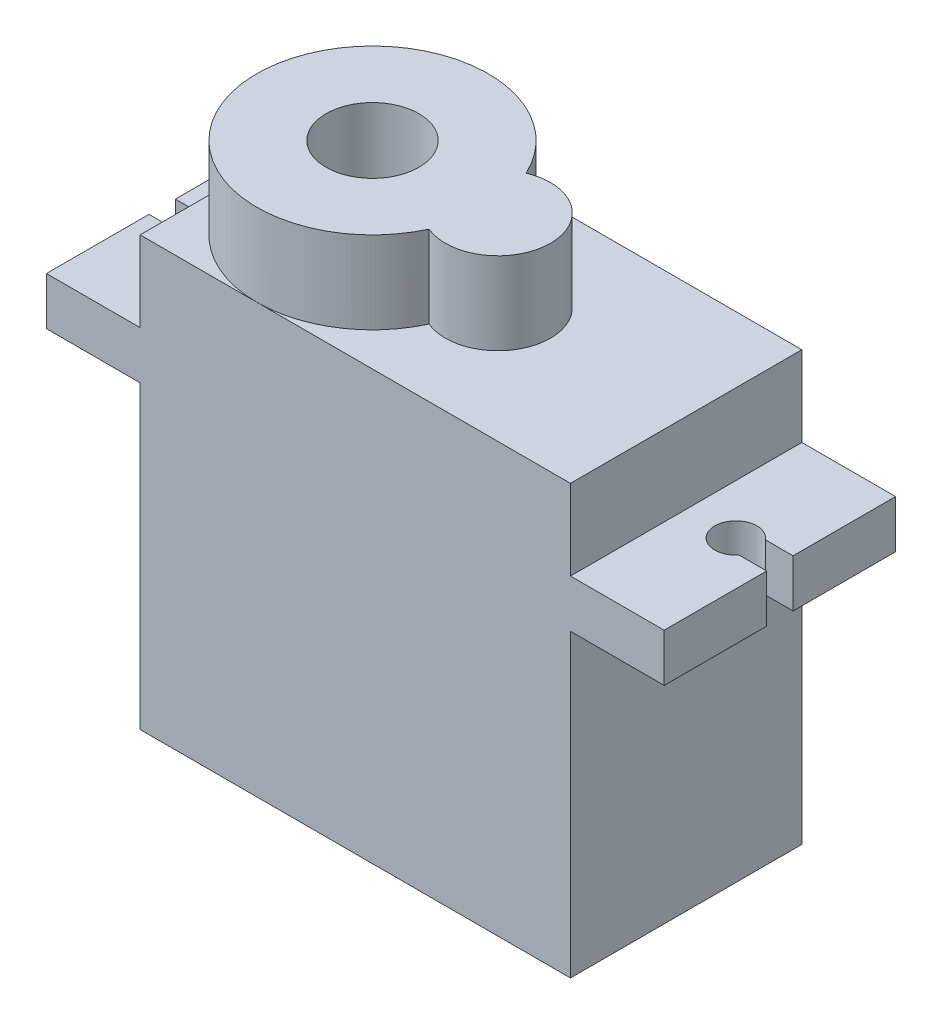
SolidWorks part; units mm, degrees
ref_plane "Front Plane" through (0, 0, 0) normal (0, 0, 1) x (1, 0, 0)
ref_plane "Top Plane" through (0, 0, 0) normal (0, 1, 0) x (1, 0, 0)
ref_plane "Right Plane" through (0, 0, 0) normal (1, 0, 0) x (0, 0, -1)
sketch "Sketch1" plane through (0, 0, 0) normal (0, 1, 0) x (1, 0, 0)
  line L1 (-22.5, -12.1) -> (22.5, -12.1)
  line L2 (-22.5, -12.1) -> (-22.5, 12.1)
  line L3 (-22.5, 12.1) -> (22.5, 12.1)
  line L4 (22.5, -12.1) -> (22.5, 12.1)
  line L5 (-22.5, -12.1) -> (22.5, 12.1) construction
  line L6 (-22.5, 12.1) -> (22.5, -12.1) construction
  point P0 (0, 0)
  dimension "D1" = 45
  dimension "D2" = 24.2
extrude "Boss-Extrude1" add sketch "Sketch1" along normal blind 44.8
sketch "Sketch2" plane through (-22.5, 0, 0) normal (-1, 0, 0) x (0, 0, 1)
  line L0 (-12.1, 0) -> (-12.1, 31.4) construction
  line L1 (-12.1, 44.8) -> (-12.1, 0) construction
  line L2 (12.1, 44.8) -> (12.1, 0) construction
  line L3 (-12.1, 31.4) -> (12.1, 31.4)
  line L4 (-12.1, 31.4) -> (-12.1, 36.4)
  line L5 (-12.1, 36.4) -> (12.1, 36.4)
  line L6 (12.1, 31.4) -> (12.1, 36.4)
  dimension "D1" = 31.4
  dimension "D2" = 5
extrude "Boss-Extrude2" add sketch "Sketch2" along normal blind 9.8
sketch "Sketch3" plane through (0, 36.4, 0) normal (0, 1, 0) x (1, 0, 0)
  line L1 (-32.3, -12.1) -> (-32.3, 12.1) construction
  line L2 (-32.3, 1.381) -> (-29.4125, 1.381)
  line L3 (-32.3, -1.381) -> (-29.4125, -1.381)
  arc A0 (-29.4125, -1.381) -> (-29.4125, 1.381) centre (-27.7, 0) ccw
  dimension "D2" = 4.4
extrude "Cut-Extrude1" cut sketch "Sketch3" against normal through all and the other way through all
ref_plane "Plane1" through (0, 0, 0) normal (-1, 0, 0) x (0, 0, 1)
mirror "Mirror2" about plane through (0, 0, 0) normal (-1, 0, 0) of "Cut-Extrude1", "Boss-Extrude2"
sketch "Sketch4" plane through (0, 44.8, 0) normal (0, 1, 0) x (1, 0, 0)
  line L0 (-27.7, 0) -> (-10.3, 0) construction
  line L1 (-10.3, 0) -> (22.5, 0) construction
  line L2 (22.5, -12.1) -> (22.5, 12.1) construction
  circle A0 centre (-10.3, 0) radius 4.86
  arc A1 (0.6863, 5.0706) -> (0.6863, -5.0706) centre (-10.3, 0) ccw
  arc A2 (0.6863, -5.0706) -> (0.6863, 5.0706) centre (2.8169, 0) ccw
  point P11 (4.8428, 0)
  point P12 (0, 0)
  point P13 (0, 0)
  point P14 (2.8169, 0)
  dimension "D2" = 9.72
  dimension "D3" = 11
  dimension "D1" = 17.4
extrude "Boss-Extrude3" add sketch "Sketch4" along normal blind 8.6
sketch "Sketch5" plane through (0, 0, 0) normal (0, -1, 0) x (1, 0, 0)
  circle A0 centre (-20.5, 10.1) radius 1.5
  circle A1 centre (20.5, 10.1) radius 1.5
  circle A2 centre (20.5, -10.1) radius 1.5
  circle A3 centre (-20.5, -10.1) radius 1.5
  dimension "D1" = 3
  dimension "D2" = 2
  dimension "D3" = 2
extrude "Cut-Extrude2" cut sketch "Sketch5" against normal blind 3
